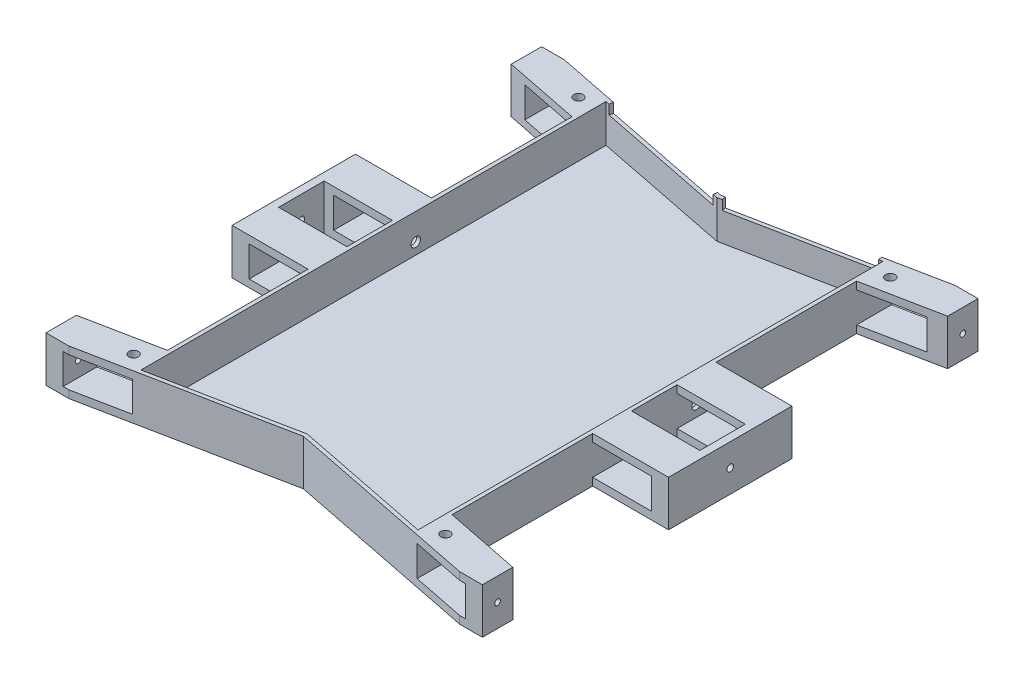
SolidWorks part; units mm, degrees
material "ABS"
ref_plane "Front Plane" through (0, 0, 0) normal (0, 0, 1) x (1, 0, 0)
ref_plane "Top Plane" through (0, 0, 0) normal (0, 1, 0) x (1, 0, 0)
ref_plane "Right Plane" through (0, 0, 0) normal (1, 0, 0) x (0, 0, -1)
sketch "Sketch1" plane through (0, 0, 0) normal (0, 1, 0) x (1, 0, 0)
  line L1 (-55, 0) -> (55, 0) construction
  line L2 (115, 32.5) -> (115, -32.5)
  line L3 (115, -32.5) -> (75, -32.5)
  line L4 (75, -32.5) -> (75, -106.6)
  line L5 (75, -106.6) -> (115, -114.6)
  line L6 (115, -114.6) -> (115, -130.6)
  line L7 (115, -130.6) -> (103, -130.6)
  line L8 (103, -130.6) -> (0, -110)
  line L9 (0, -55) -> (0, 55) construction
  line L11 (-115, 32.5) -> (-115, -32.5)
  line L12 (-115, -32.5) -> (-75, -32.5)
  line L13 (-75, -32.5) -> (-75, -106.6)
  line L14 (-75, -106.6) -> (-115, -114.6)
  line L15 (-115, -114.6) -> (-115, -130.6)
  line L16 (-115, -130.6) -> (-103, -130.6)
  line L17 (-103, -130.6) -> (0, -110)
  line L18 (115, 32.5) -> (75, 32.5)
  line L19 (75, 32.5) -> (75, 106.6)
  line L20 (115, 130.6) -> (103, 130.6)
  line L21 (115, 114.6) -> (115, 130.6)
  line L22 (75, 106.6) -> (115, 114.6)
  line L23 (103, 130.6) -> (0, 110)
  line L24 (-115, 114.6) -> (-115, 130.6)
  line L25 (-115, 130.6) -> (-103, 130.6)
  line L26 (-103, 130.6) -> (0, 110)
  line L27 (-75, 106.6) -> (-115, 114.6)
  line L28 (-115, 32.5) -> (-75, 32.5)
  line L29 (-75, 32.5) -> (-75, 106.6)
  line L30 (75, -106.6) -> (75, -125) construction
  line L32 (-75, -106.6) -> (-75, -125) construction
  line L34 (-75, 106.6) -> (-75, 125) construction
  line L36 (75, 106.6) -> (75, 125) construction
  point P21 (115, 0)
  point P33 (-115, 0)
  dimension "D1" = 250
  dimension "D2" = 220
  dimension "D3" = 150
  dimension "D4" = 16
  dimension "D5" = 12
  dimension "D6" = 65
  dimension "D7" = 40
extrude "Boss-Extrude1" add sketch "Sketch1" along normal blind 12 and the other way blind 12
sketch "Sketch2" plane through (0, 0, 130.6) normal (0, 0, 1) x (1, 0, 0)
  line L0 (-115, -12) -> (-115, 12) construction
  line L1 (-106, -8) -> (106, -8)
  line L2 (-106, -8) -> (-106, 8)
  line L3 (-106, 8) -> (106, 8)
  line L4 (106, -8) -> (106, 8)
  line L5 (115, -12) -> (115, 12) construction
  line L7 (55, 0) -> (-55, 0) construction
  dimension "D1" = 8
  dimension "D2" = 8
  dimension "D3" = 9
  dimension "D4" = 9
extrude "Cut-Extrude1" cut sketch "Sketch2" against normal blind 320
sketch "Sketch4" plane through (0, 12, 0) normal (0, 1, 0) x (1, 0, 0)
  line L0 (-55, 0) -> (55, 0) construction
  line L1 (-111, 12) -> (-75, 12)
  line L2 (-111, 12) -> (-111, -12)
  line L3 (-111, -12) -> (-75, -12)
  line L4 (-75, 12) -> (-75, -12)
  line L5 (-115, 32.5) -> (-115, -32.5) construction
  line L6 (-75, -32.5) -> (-75, -106.6) construction
  line L7 (0, -55) -> (0, 55) construction
  line L8 (111, -12) -> (75, -12)
  line L9 (75, 12) -> (75, -12)
  line L10 (111, 12) -> (75, 12)
  line L11 (111, 12) -> (111, -12)
  dimension "D1" = 12
  dimension "D2" = 12
  dimension "D3" = 4
extrude "Cut-Extrude2" cut sketch "Sketch4" against normal blind 24
sketch "Sketch6" plane through (0, 0, 0) normal (1, 0, 0) x (0, 0, -1)
  line L0 (-114.6, 0) -> (-130.6, 0) construction
  line L1 (114.6, 0) -> (130.6, 0) construction
  circle A0 centre (-122.6, 0) radius 1.5
  circle A1 centre (122.6, 0) radius 1.5
  point P6 (-122.6, 0)
  point P10 (122.6, 0)
  dimension "D1" = 3
extrude "Cut-Extrude3" cut sketch "Sketch6" against normal through all both and the other way through all
sketch "Sketch7" plane through (115, 0, 0) normal (1, 0, 0) x (0, 0, -1)
  circle A0 centre (0, 0) radius 1.75
  dimension "D1" = 3.5
extrude "Cut-Extrude4" cut sketch "Sketch7" against normal up to surface (230 mm away) up to face at (-115, 0, 0)
sketch "Sketch8" plane through (0, 12, 0) normal (0, 1, 0) x (1, 0, 0)
  line L0 (0, 110) -> (0, -110) construction
  line L1 (106, -12) -> (106, 12) construction
  line L2 (106, 8) -> (94, 8)
  line L3 (106, 8) -> (106, -8)
  line L4 (106, -8) -> (94, -8)
  line L5 (94, 8) -> (94, -8)
  line L6 (-106, 0) -> (115, 0) construction
  line L7 (-106, 12) -> (-106, -12) construction
  line L8 (115, -32.5) -> (115, 32.5) construction
  line L9 (-106, -8) -> (-94, -8)
  line L10 (-94, 8) -> (-94, -8)
  line L11 (-106, 8) -> (-94, 8)
  line L12 (-106, 8) -> (-106, -8)
  point P16 (94, 0)
  dimension "D1" = 16
  dimension "D2" = 12
extrude "Cut-Extrude5" [suppressed] cut sketch "Sketch8" against normal up to surface (5 mm away) up to face at (0, 8, 0)
sketch "Sketch11" plane through (0, 12, 0) normal (0, 1, 0) x (1, 0, 0)
  line L0 (-75, -125) -> (-75, 125)
  line L1 (-103, -130.6) -> (0, -110) construction
  line L2 (0, 110) -> (-103, 130.6) construction
  line L3 (75, 125) -> (75, -125)
  line L4 (103, 130.6) -> (0, 110) construction
  line L5 (0, -110) -> (103, -130.6) construction
  line L6 (75, 32.5) -> (75, 106.6) construction
  line L7 (-75, 106.6) -> (-75, 32.5) construction
  line L8 (0, -110) -> (75, -125)
  line L9 (-75, -125) -> (0, -110)
  line L10 (0, 110) -> (-75, 125)
  line L11 (75, 125) -> (0, 110)
extrude "Cut-Extrude7" cut sketch "Sketch11" against normal up to surface (4 mm away) up to face at (0, 8, 0)
sketch "Sketch12" plane through (0, -8, 0) normal (0, 1, 0) x (1, 0, 0)
  line L0 (-75, 125) -> (-75, -125)
  line L1 (-103, -130.6) -> (0, -110) construction
  line L2 (75, 125) -> (75, -125)
  line L3 (-75, -125) -> (0, -110)
  line L4 (0, -110) -> (75, -125)
  line L5 (-75, 125) -> (0, 110)
  line L6 (0, 110) -> (75, 125)
  line L7 (0, 107.9604) -> (73, 122.5604)
  line L8 (73, 122.5604) -> (73, -122.5604)
  line L9 (0, -107.9604) -> (73, -122.5604)
  line L10 (-73, -122.5604) -> (0, -107.9604)
  line L11 (-73, 122.5604) -> (-73, -122.5604)
  line L12 (-73, 122.5604) -> (0, 107.9604)
  dimension "D1" = 2
extrude "Boss-Extrude2" add sketch "Sketch12" along normal blind 20
sketch "Sketch14" plane through (0, 12, 0) normal (0, 1, 0) x (1, 0, 0)
  line L0 (0, 110) -> (0, -110) construction
  line L1 (75, 0) -> (-75, 0) construction
  line L2 (75, -12) -> (75, 12) construction
  line L3 (-75, 12) -> (-75, -12) construction
  line L4 (-83.9461, 108.3892) -> (-80.4076, 126.0815) construction
  line L5 (-115, 114.6) -> (-75, 106.6) construction
  line L6 (0, 110) -> (-103, 130.6) construction
  circle A0 centre (-82.1768, 117.2354) radius 2.5
  circle A1 centre (82.1768, 117.2354) radius 2.5
  circle A2 centre (82.1768, -117.2354) radius 2.5
  circle A3 centre (-82.1768, -117.2354) radius 2.5
  dimension "D2" = 5
  dimension "D1" = 82
extrude "Cut-Extrude8" cut sketch "Sketch14" against normal up to next
sketch "Sketch15" plane through (0, 12, 0) normal (0, 1, 0) x (1, 0, 0)
  line L0 (-71.0388, 122.1682) -> (-70.6466, 124.1293)
  line L1 (0, 110) -> (-103, 130.6) construction
  line L2 (0, 107.9604) -> (-73, 122.5604) construction
  line L3 (-2.3982, 108.44) -> (-71.0388, 122.1682)
  line L4 (-2.006, 110.4012) -> (-70.6466, 124.1293)
  line L5 (73, 122.5604) -> (0, 107.9604) construction
  line L6 (103, 130.6) -> (0, 110) construction
  line L7 (71.0388, 122.1682) -> (2.3982, 108.44)
  line L8 (70.6466, 124.1293) -> (2.006, 110.4012)
  line L10 (-2.3982, 108.44) -> (-2.006, 110.4012)
  line L11 (2.3982, 108.44) -> (2.006, 110.4012)
  line L12 (70.6466, 124.1293) -> (71.0388, 122.1682)
  dimension "D1" = 70
  dimension "D2" = 70
  dimension "D3" = 2
  dimension "D4" = 2
extrude "Cut-Extrude9" cut sketch "Sketch15" against normal blind 5
sketch "Sketch16" plane through (75, 0, 0) normal (1, 0, 0) x (0, 0, -1)
  line L0 (22.25, 8) -> (22.25, -8) construction
  line L1 (32.5, 8) -> (12, 8) construction
  line L2 (12, -8) -> (32.5, -8) construction
  circle A0 centre (22.25, -2) radius 2.5
  dimension "D2" = 5
  dimension "D1" = 6
extrude "Cut-Extrude10" cut sketch "Sketch16" against normal up to surface (150 mm away) up to face at (-75, 0, 0)
equation "\"A\"= 4"
equation "\"D1@Boss-Extrude1\"=3*\"A\""
equation "\"D2@Boss-Extrude1\"=3*\"A\""
equation "\"D1@Sketch2\"=2*\"A\""
equation "\"D2@Sketch2\"=2*\"A\""
equation "\"D1@Sketch4\"=3*\"A\""
equation "\"D2@Sketch4\"=3*\"A\""
equation "\"D3@Sketch4\"=\"A\""
equation "\"D1@Cut-Extrude2\"=6*\"A\""
equation "\"D1@Cut-Extrude1\"=80*\"A\""
